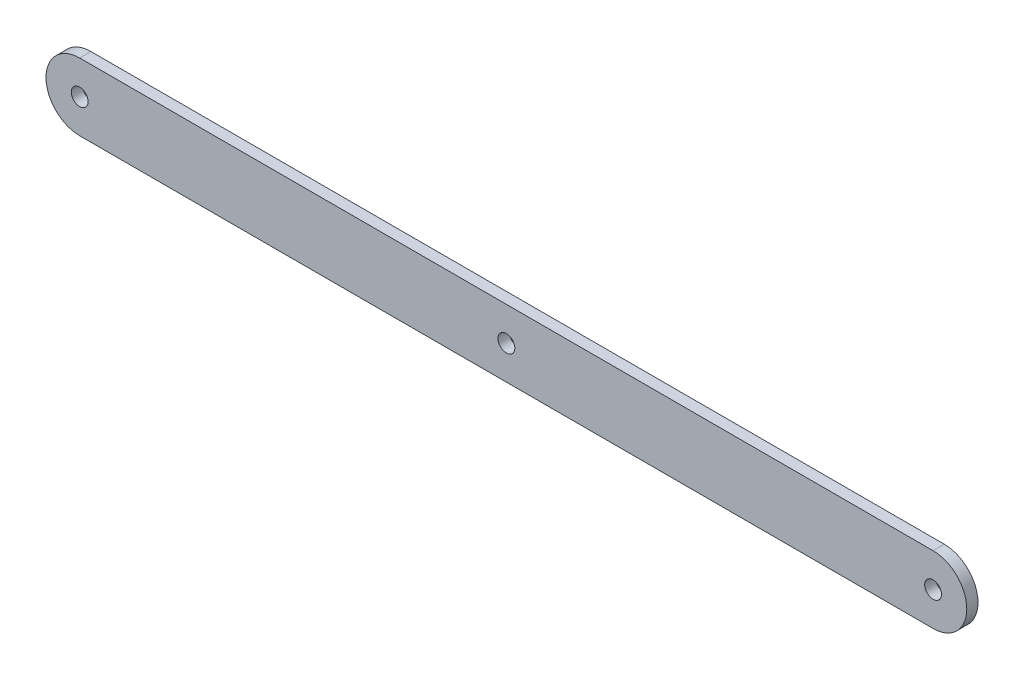
SolidWorks part; units mm, degrees
ref_plane "Front Plane" through (0, 0, 0) normal (0, 0, 1) x (1, 0, 0)
ref_plane "Top Plane" through (0, 0, 0) normal (0, 1, 0) x (1, 0, 0)
ref_plane "Right Plane" through (0, 0, 0) normal (1, 0, 0) x (0, 0, -1)
ref_axis "X" through (-88.99, 0, 0) along (1, 0, 0)
ref_axis "Y" through (0, 55, 0) along (0, -1, 0)
ref_axis "Z" through (0, 0, -88.99) along (0, 0, 1)
sketch "Sketch1" plane through (0, 0, 0) normal (0, 0, 1) x (1, 0, 0)
  line L0 (-76, 0) -> (76, 0) construction
  line L1 (-76, 6) -> (76, 6)
  line L2 (-76, -6) -> (76, -6)
  line L4 (-10, 6) -> (10, 6) construction
  arc A0 (-76, 6) -> (-76, -6) centre (-76, 0) ccw
  arc A1 (76, -6) -> (76, 6) centre (76, 0) ccw
  circle A2 centre (-76, 0) radius 1.5
  circle A3 centre (0, 0) radius 1.5
  circle A4 centre (76, 0) radius 1.5
  circle A5 centre (-76, 0) radius 1.5 construction
  point P2 (0, 0)
  point P14 (-76, 0)
extrude "Boss-Extrude1" add sketch "Sketch1" along normal blind 2
